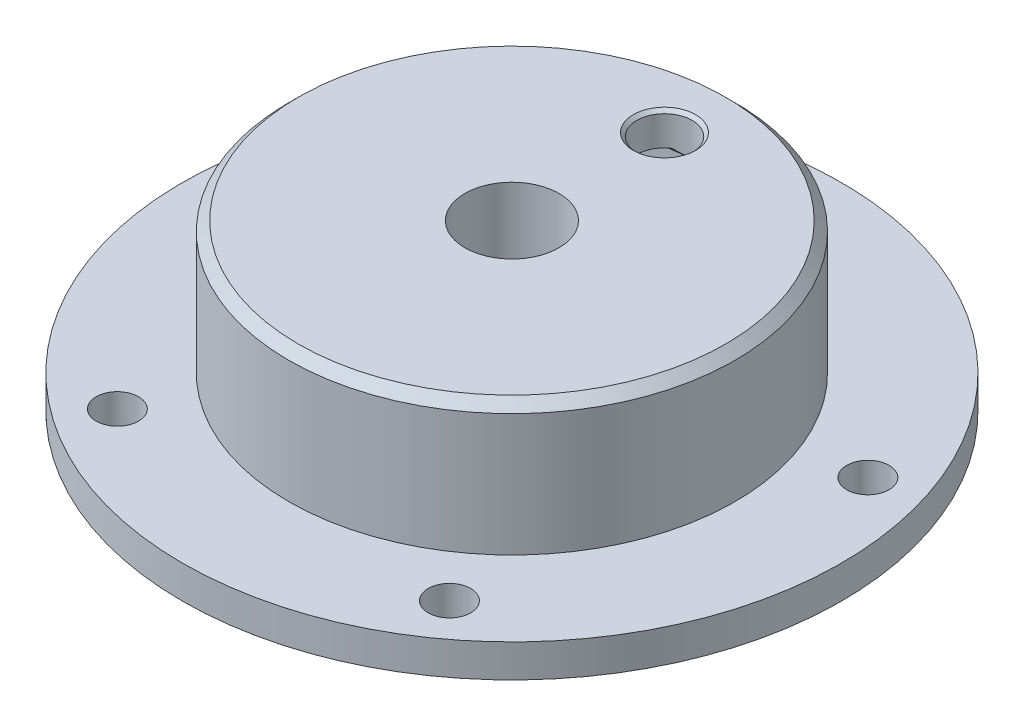
SolidWorks part; units mm, degrees
material "1023 Carbon Steel Sheet (SS)"
ref_plane "Front Plane" through (0, 0, 0) normal (0, 0, 1) x (1, 0, 0)
ref_plane "Top Plane" through (0, 0, 0) normal (0, 1, 0) x (1, 0, 0)
ref_plane "Right Plane" through (0, 0, 0) normal (1, 0, 0) x (0, 0, -1)
sketch "Sketch1" plane through (0, 0, 0) normal (0, 0, 1) x (1, 0, 0)
  line L0 (0, 0) -> (-10, 0) construction
  line L1 (-10, 0) -> (-10, -35)
  line L2 (-10, -35) -> (-12.5, -35)
  line L3 (-12.5, -35) -> (-12.5, -33.2)
  line L4 (-12.7, -33) -> (-15.542, -33)
  line L5 (-15.75, -33.208) -> (-15.75, -35)
  line L6 (-15.75, -35) -> (-18.5, -35)
  line L7 (-18.5, -35) -> (-18.5, -33.208)
  line L8 (-18.708, -33) -> (-21.542, -33)
  line L9 (-21.75, -33.208) -> (-21.75, -35)
  line L10 (-21.75, -35) -> (-24, -35)
  line L11 (-24, -35) -> (-24, -7)
  line L13 (-39.4, -7) -> (-39.4, -35)
  line L14 (-39.4, -35) -> (-42, -35)
  line L15 (-42, -35) -> (-42, -33.208)
  line L16 (-42.208, -33) -> (-45.042, -33)
  line L17 (-45.25, -33.208) -> (-45.25, -35)
  line L18 (-45.25, -35) -> (-47.75, -35)
  line L19 (-47.75, -35) -> (-47.75, -33.208)
  line L20 (-47.958, -33) -> (-50.792, -33)
  line L21 (-51, -33.208) -> (-51, -35)
  line L22 (-51, -35) -> (-70, -35)
  line L23 (-70, -35) -> (-70, -28)
  line L24 (-70, -28) -> (-47.4, -28)
  line L25 (-47.4, -28) -> (-47.4, 0)
  line L26 (-47.4, 0) -> (-10, 0)
  line L28 (-39.4, -7) -> (-24, -7)
  line L29 (0, 0) -> (0, -83.2336) construction
  arc A0 (-12.5, -33.2) -> (-12.7, -33) centre (-12.7, -33.2) ccw
  arc A1 (-15.542, -33) -> (-15.75, -33.208) centre (-15.542, -33.208) ccw
  arc A2 (-21.542, -33) -> (-21.75, -33.208) centre (-21.542, -33.208) ccw
  arc A3 (-18.5, -33.208) -> (-18.708, -33) centre (-18.708, -33.208) ccw
  arc A4 (-50.792, -33) -> (-51, -33.208) centre (-50.792, -33.208) ccw
  arc A5 (-47.75, -33.208) -> (-47.958, -33) centre (-47.958, -33.208) ccw
  arc A6 (-45.042, -33) -> (-45.25, -33.208) centre (-45.042, -33.208) ccw
  arc A7 (-42, -33.208) -> (-42.208, -33) centre (-42.208, -33.208) ccw
  point P30 (-12.5, -33)
  point P33 (-15.75, -33)
  point P36 (-21.75, -33)
  point P39 (-18.5, -33)
  point P42 (-51, -33)
  point P45 (-47.75, -33)
  point P48 (-45.25, -33)
  point P51 (-42, -33)
  dimension "D26" = 0.2
  dimension "D27" = 0.208
  dimension "D28" = 0.208
  dimension "D29" = 0.208
  dimension "D1" = 10
  dimension "D2" = 35
  dimension "D3" = 2.5
  dimension "D4" = 2
  dimension "D5" = 3.25
  dimension "D6" = 2
  dimension "D7" = 2.75
  dimension "D8" = 2
  dimension "D9" = 3.25
  dimension "D10" = 2
  dimension "D11" = 2.25
  dimension "D12" = 28
  dimension "D13" = 15.4
  dimension "D14" = 28
  dimension "D15" = 28
  dimension "D16" = 22.6
  dimension "D17" = 7
  dimension "D18" = 2.6
  dimension "D19" = 2
  dimension "D20" = 3.25
  dimension "D21" = 2.5
  dimension "D22" = 2
  dimension "D23" = 2
  dimension "D24" = 3.25
  dimension "D25" = 37.4
revolve "Revolve1" add sketch "Sketch1" angle 360 about L29
sketch "Sketch2" plane through (0, 0, 0) normal (0, 1, 0) x (1, 0, 0)
  point P0 (0, 32.4)
  dimension "D1" = 32.4
hole_wizard "G1/4 Tapped Hole1" positions "Sketch3" profile "Sketch4" tap size "G1/4" standard "BSI" end condition up to next
sketch "Sketch3" plane through (0, 0, 0) normal (0, 1, 0) x (1, 0, 0)
  point P0 (0, 32.4)
sketch "Sketch4" plane through (0, 0, -32.4) normal (1, 0, 0) x (0, 0, 1)
  line L0 (0, 0) -> (0, 7)
  line L1 (0, 7) -> (5.9, 7)
  line L2 (5.9, 7) -> (5.9, 0.7035)
  line L3 (5.9, 0.7035) -> (6.6035, 0)
  line L5 (6.6035, 0) -> (0, 0)
  line L6 (-5.9, 0.7035) -> (-6.6035, 0) construction
  line L11 (0, -6.35) -> (0, 107.95) construction
  dimension "Thru Tap Drill Dia." = 11.8
  dimension "Thru Tap Drill Depth" = 7
  dimension "Near C'Sink Dia." = 13.207
  dimension "Near C'Sink Angle" = 90
cosmetic thread "Hole Thread1" parameters "D2"=13.157
sketch "Sketch5" plane through (0, -28, 0) normal (0, 1, 0) x (1, 0, 0)
  circle A0 centre (0, 60) radius 4.5
  point P0 (0, 60)
  dimension "D1" = 60
extrude "Cut-Extrude1" cut sketch "Sketch5" against normal blind 10
sketch "Sketch6" plane through (0, 0, 0) normal (0, 0, 1) x (1, 0, 0)
  line L0 (0, -22.7338) -> (0, 22.818) construction
pattern_circular "CirPattern1" count 5 over 360 about axis through (0, -22.7338, 0) along (0, 1, 0) of "Cut-Extrude1" reverse direction yes
chamfer "Chamfer1" distance 2 angle 45 3 edges at (0, -7, 39.4) (0, 0, 47.4) (0, -7, 24)
